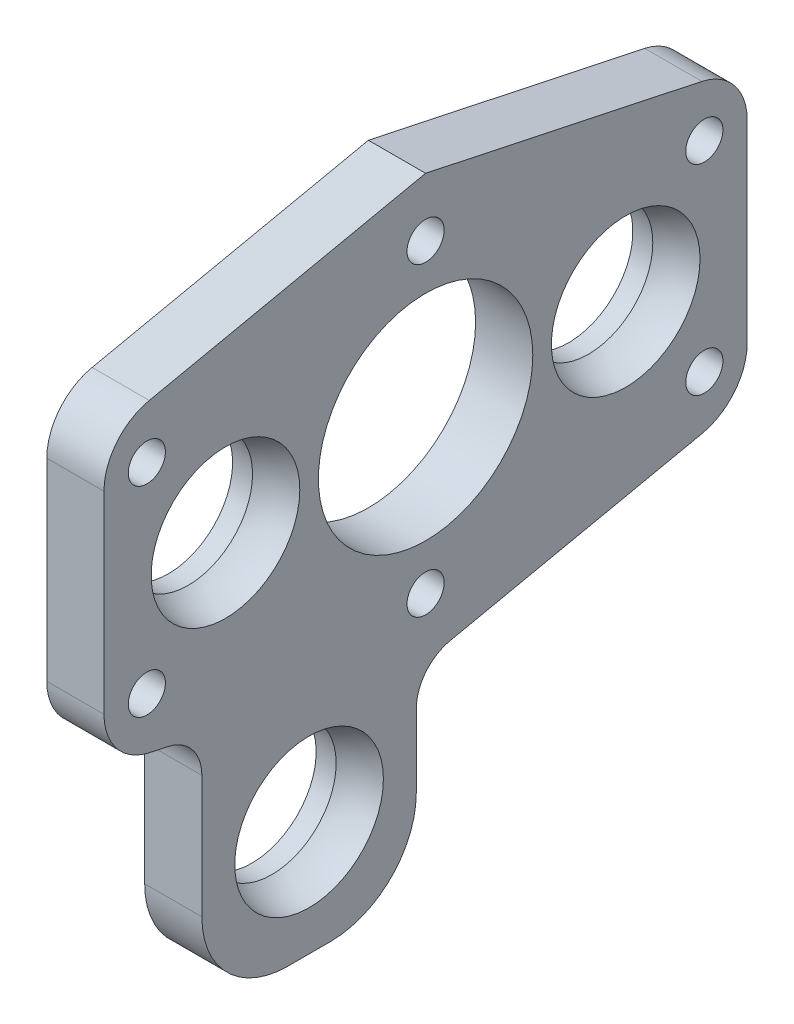
SolidWorks part; units mm, degrees
ref_plane "Front" through (0, 0, 0) normal (0, 0, 1) x (1, 0, 0)
ref_plane "Top" through (0, 0, 0) normal (0, 1, 0) x (1, 0, 0)
ref_plane "Right" through (0, 0, 0) normal (1, 0, 0) x (0, 0, -1)
sketch "Sketch1" plane through (0, 0, 0) normal (1, 0, 0) x (0, 0, -1)
  line L0 (0, 0) -> (22.5, 4.7697)
  line L1 (0, 0) -> (45, 0)
  line L2 (0, 0) -> (0, -20)
  line L3 (0, -20) -> (45, -20)
  line L4 (45, 0) -> (45, -20)
  line L5 (22.5, 4.7697) -> (45, 0)
  line L6 (0, -20) -> (22.5, -24.7697)
  line L7 (22.5, -24.7697) -> (45, -20)
  circle A0 centre (22.5, 0.6808) radius 1.3
  circle A1 centre (22.5, -20.6808) radius 1.3
  circle A2 centre (3, -3) radius 1.3
  circle A3 centre (42, -3) radius 1.3
  circle A4 centre (42, -17) radius 1.3
  circle A5 centre (3, -17) radius 1.3
  dimension "D7" = 2.6
  dimension "D8" = 2.6
  dimension "D13" = 2.6
  dimension "D1" = 45
  dimension "D2" = 20
  dimension "D3" = 23
  dimension "D4" = 23
  dimension "D5" = 23
  dimension "D6" = 23
  dimension "D9" = 4
  dimension "D10" = 4
  dimension "D11" = 4
  dimension "D12" = 4
  dimension "D14" = 3
  dimension "D15" = 3
  dimension "D16" = 2
  dimension "D17" = 2
extrude "Boss-Extrude1" add sketch "Sketch1" along normal blind 4 contours L4 L1 L2 L3 | L5 L0 L1 A0 | L6 L7 L3 A1 region at (0, 1.9422, -11.3438) region at (0, -10, -22.5) region at (0, -20.4525, -10.6963)
sketch "Sketch2" plane through (4, 0, 0) normal (1, 0, 0) x (0, 0, -1)
  line L0 (0, 0) -> (0, -20) construction
  line L1 (3.3, -10) -> (13.7, -10)
  line L2 (31.3, -10) -> (41.7, -10)
  arc A0 (13.7, -10) -> (3.3, -10) centre (8.5, -10) ccw
  arc A1 (41.7, -10) -> (31.3, -10) centre (36.5, -10) ccw
  dimension "D1" = 10.4
  dimension "D2" = 8.5
  dimension "D3" = 10
  dimension "D4" = 2
revolve "Cut-Revolve1" cut sketch "Sketch2" angle 360 about L1
sketch "Sketch3" plane through (4, 0, 0) normal (1, 0, 0) x (0, 0, -1)
  line L0 (0, 0) -> (0, -20) construction
  circle A0 centre (22.5, -10) radius 7.5
  dimension "D1" = 15
  dimension "D2" = 22.5
  dimension "D3" = 10
extrude "Cut-Extrude1" cut sketch "Sketch3" against normal through all
sketch "Sketch4" plane through (0, 0, 0) normal (-1, 0, 0) x (0, 0, 1)
  circle A0 centre (-8.5, -10) radius 4.5
  circle A1 centre (-36.5, -10) radius 4.5
  circle A2 centre (-36.5, -10) radius 3.3226 construction
  circle A3 centre (-8.5, -10) radius 3.3226 construction
  point P4 (0, 0)
  dimension "D1" = 9
  dimension "D2" = 9
  dimension "D3" = 0
  dimension "D4" = 0
extrude "Cut-Extrude2" cut sketch "Sketch4" against normal through all
sketch "Sketch5" plane through (4, 0, 0) normal (1, 0, 0) x (0, 0, -1)
  line L0 (6.8478, -21.4516) -> (21.8478, -24.6314)
  line L1 (0, -20) -> (22.5, -24.7697) construction
  line L2 (21.8478, -24.6314) -> (21.8478, -38.4516)
  line L3 (21.8478, -38.4516) -> (6.8478, -38.4516)
  line L4 (6.8478, -38.4516) -> (6.8478, -21.4516)
  dimension "D1" = 15
  dimension "D2" = 17
  dimension "D3" = 7
extrude "Boss-Extrude2" add sketch "Sketch5" against normal blind 4
sketch "Sketch6" plane through (4, 0, 0) normal (1, 0, 0) x (0, 0, -1)
  line L0 (6.8478, -21.4516) -> (6.8478, -38.4516) construction
  line L1 (6.8478, -38.4516) -> (21.8478, -38.4516) construction
  line L2 (14.3478, -25.2516) -> (14.3478, -35.6516)
  arc A0 (14.3478, -25.2516) -> (14.3478, -35.6516) centre (14.3478, -30.4516) ccw
  dimension "D1" = 10.4
  dimension "D2" = 7.5
  dimension "D3" = 8
revolve "Cut-Revolve2" cut sketch "Sketch6" angle 360 about L2
sketch "Sketch7" plane through (0, 0, 0) normal (-1, 0, 0) x (0, 0, 1)
  circle A0 centre (-14.3478, -30.4516) radius 4.5
  circle A1 centre (-14.3478, -30.4516) radius 3.3226 construction
  dimension "D1" = 9
  dimension "D2" = 0
extrude "Cut-Extrude3" cut sketch "Sketch7" against normal through all
fillet "Fillet1" radius 6 2 edges at (2, -38.4516, -21.8478) (2, -38.4516, -6.8478)
fillet "Fillet2" radius 4 4 edges at (2, 0, 0) (2, -20, 0) (2, -20, -45) (2, 0, -45)
fillet "Fillet3" radius 3 2 edges at (2, -24.6314, -21.8478) (2, -21.4516, -6.8478)
fillet "Fillet4" radius 3 1 edges at (2, -24.7697, -22.5)
